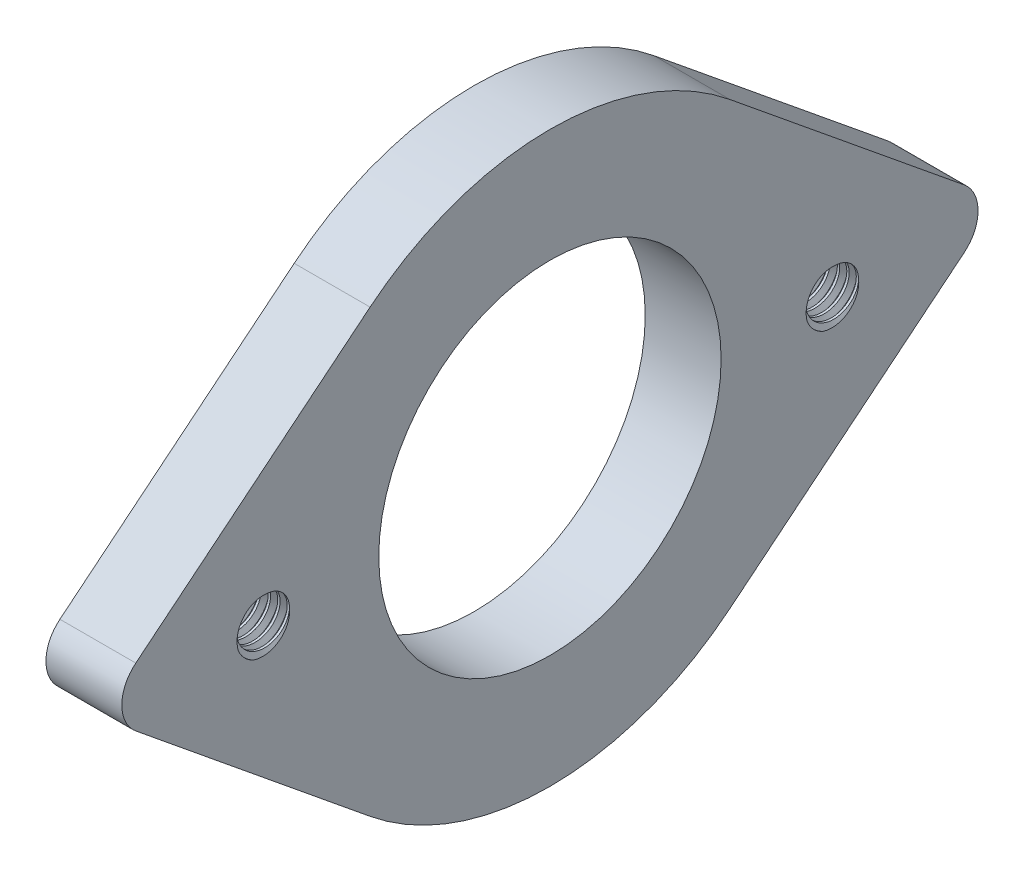
SolidWorks part; units mm, degrees
ref_plane "Alzado" through (0, 0, 0) normal (0, 0, 1) x (1, 0, 0)
ref_plane "Planta" through (0, 0, 0) normal (0, 1, 0) x (1, 0, 0)
ref_plane "Vista lateral" through (0, 0, 0) normal (1, 0, 0) x (0, 0, -1)
sketch "Croquis1" plane through (0, 0, 0) normal (0, 0, 1) x (1, 0, 0)
  line L1 (-12.7, -25.4) -> (12.7, -25.4)
  line L2 (-12.7, -25.4) -> (-12.7, 25.4)
  line L3 (-12.7, 25.4) -> (12.7, 25.4)
  line L4 (12.7, -25.4) -> (12.7, 25.4)
  line L5 (-12.7, -25.4) -> (12.7, 25.4) construction
  line L6 (-12.7, 25.4) -> (12.7, -25.4) construction
  line L7 (11.1125, -23.8125) -> (-11.1125, -23.8125)
  line L8 (11.1125, -23.8125) -> (11.1125, 23.8125)
  line L9 (11.1125, 23.8125) -> (-11.1125, 23.8125)
  line L10 (-11.1125, -23.8125) -> (-11.1125, 23.8125)
  line L11 (11.1125, -23.8125) -> (-11.1125, 23.8125) construction
  line L12 (11.1125, 23.8125) -> (-11.1125, -23.8125) construction
  point P0 (0, 0)
  point P6 (0, 0)
  dimension "D1" = 25.4
  dimension "D2" = 50.8
  dimension "D3" = 1.5875
  dimension "D4" = 1.5875
extrude "Saliente-Extruir1" add sketch "Croquis1" along normal mid plane 406.4
sketch "Croquis2" plane through (-12.7, 0, 0) normal (-1, 0, 0) x (0, 0, 1)
  line L0 (203.2, -25.4) -> (-203.2, -25.4) construction
  line L1 (-176.2125, 0) -> (-128.5875, 0) construction
  line L2 (-203.2, 25.4) -> (-203.2, -25.4) construction
  line L3 (-152.5177, 19.0982) -> (115.4773, 20.7492) construction
  line L5 (-152.2823, -19.0982) -> (115.7126, -17.4472) construction
  line L6 (104.4824, -15.8115) -> (126.7074, -15.8115)
  line L7 (98.1324, -9.4615) -> (98.1324, 12.7635)
  line L8 (104.4824, 19.1135) -> (126.7074, 19.1135)
  line L9 (133.0574, -9.4615) -> (133.0574, 12.7635)
  line L10 (98.1324, -15.8115) -> (133.0574, 19.1135) construction
  line L11 (98.1324, 19.1135) -> (133.0574, -15.8115) construction
  circle A0 centre (-152.4, 0) radius 23.8125 construction
  circle A1 centre (-152.4, 0) radius 19.1135
  circle A2 centre (-176.2125, 0) radius 2.4892
  circle A3 centre (-128.5875, 0) radius 2.4892
  arc A7 (126.7074, -15.8115) -> (133.0574, -9.4615) centre (126.7074, -9.4615) ccw
  arc A8 (126.7074, 19.1135) -> (133.0574, 12.7635) centre (126.7074, 12.7635) cw
  arc A9 (104.4824, -15.8115) -> (98.1324, -9.4615) centre (104.4824, -9.4615) cw
  arc A10 (98.1324, 12.7635) -> (104.4824, 19.1135) centre (104.4824, 12.7635) cw
  circle A11 centre (115.5949, 1.651) radius 23.8125 construction
  circle A12 centre (91.7824, 1.651) radius 2.4892
  circle A13 centre (139.4074, 1.651) radius 2.4892
  arc A14 (-152.5177, 19.0982) -> (-152.2823, -19.0982) centre (-152.4, 0) ccw construction
  arc A16 (115.7126, -17.4472) -> (115.4773, 20.7492) centre (115.5949, 1.651) ccw construction
  point P7 (-152.4, 0)
  point P9 (115.5949, 1.651)
  point P17 (-152.4, 0)
  dimension "D1" = 47.625
  dimension "D3" = 38.227
  dimension "D4" = 4.9784
  dimension "D7" = 6.35
  dimension "D9" = 38.1972
  dimension "D2" = 1.5875
  dimension "D6" = 34.925
  dimension "D8" = 1.651
  dimension "D5" = 50.8
extrude "Cortar-Extruir1" cut sketch "Croquis2" against normal through all
sketch "Croquis3" plane through (-12.7, 0, 0) normal (-1, 0, 0) x (0, 0, 1)
  line L0 (-152.4, 0) -> (-188.2267, 0) construction
  line L1 (-187.0585, -2.4604) -> (-167.4507, -18.453)
  line L2 (-167.4507, 18.453) -> (-187.0585, 2.4604)
  line L3 (-152.4, 23.8125) -> (-152.4, -23.8125) construction
  line L4 (-137.3493, 18.453) -> (-117.7415, 2.4604)
  line L5 (-117.7415, -2.4604) -> (-137.3493, -18.453)
  circle A0 centre (-176.2125, 0) radius 2.0193
  circle A1 centre (-152.4, 0) radius 23.8125
  arc A3 (-187.0585, 2.4604) -> (-187.0585, -2.4604) centre (-185.0517, 0) ccw
  arc A4 (-117.7415, 2.4604) -> (-117.7415, -2.4604) centre (-119.7483, 0) cw
  circle A5 centre (-128.5875, 0) radius 2.0193
  circle A6 centre (-152.4, 0) radius 14.3256
  circle M11 centre (-128.5875, 0) radius 2.4892
  circle M12 centre (-176.2125, 0) radius 2.4892
  circle M13 centre (-152.4, 0) radius 19.1135
  dimension "D1" = 47.625
  dimension "D2" = 4.0386
  dimension "D4" = 3.175
  dimension "D5" = 28.6512
  dimension "D3" = 35.8267
extrude "Saliente-Extruir2" add sketch "Croquis3" along normal blind 6.35 separate body contours L2 A3 L1 A1 M12 | A1 M11 M12 M13 | A4 L4 A1 L5 M11 | A1 A0 M12 | A1 A0 M12 | A1 A5 M11 | A1 A5 M11 | A6 M13 region at (-12.7, 0, -179.5987) region at (-12.7, -11.0047, -172.7567) region at (-12.7, 0, -125.2013) region at (-12.7, 0, -178.6454) region at (-12.7, -2.2465, -176.0508) region at (-12.7, 0, -131.0215) region at (-12.7, -2.2571, -128.6382) region at (-12.7, 0, -170.9729)
thread "Rosca1" pitch 0.7937 method cut profile "Perfil de rosca1" start angle 0, offset 0, length 0, pitch 0.7937, diameter 4.0386
ref_plane "Plano1" through (-19.05, 0, -130.6068) normal (0, -1, 0) x (0, 0, -1)
sketch "Perfil de rosca1" plane through (-19.05, 0, -130.6068) normal (0, -1, 0) x (0, 0, -1)
  line L0 (0, 0) -> (0, 0.7937) construction
  line L1 (0, 0) -> (0.4296, 0.248)
  line L2 (0.4296, 0.248) -> (0.4296, 0.3473)
  line L3 (0.4296, 0.3473) -> (0, 0.5953)
  line L4 (0.4296, 0.2977) -> (0, 0.2977) construction
  line L11 (0, 0) -> (0, 0.5953)
  point P2 (0, 0)
  dimension "Pitch" = 0.7937
  dimension "Profile_Angle" = 60
  dimension "Profile_Land" = 0.0992
  dimension "Profile_Height" = 0.4296
thread "Rosca2" pitch 0.7937 method cut profile "Perfil de rosca2" start angle 0, offset 0, length 0, pitch 0.7937, diameter 4.0386
ref_plane "Plano2" through (-19.05, 0, -178.2318) normal (0, -1, 0) x (0, 0, -1)
sketch "Perfil de rosca2" plane through (-19.05, 0, -178.2318) normal (0, -1, 0) x (0, 0, -1)
  line L0 (0, 0) -> (0, 0.7937) construction
  line L1 (0, 0) -> (0.4296, 0.248)
  line L2 (0.4296, 0.248) -> (0.4296, 0.3473)
  line L3 (0.4296, 0.3473) -> (0, 0.5953)
  line L4 (0.4296, 0.2977) -> (0, 0.2977) construction
  line L11 (0, 0) -> (0, 0.5953)
  point P2 (0, 0)
  dimension "Pitch" = 0.7937
  dimension "Profile_Angle" = 60
  dimension "Profile_Land" = 0.0992
  dimension "Profile_Height" = 0.4296
delete or keep bodies "Sólido-Eliminar/Conservar 1" type keep bodies bodies 105
delete or keep bodies "Sólido-Eliminar/Conservar 2" [suppressed] type keep bodies bodies 102
equation "\"D9@Croquis2\"=(24*5mm)/pi"
equation "\"D10@Croquis2\"=(131*5mm)+1mm"
